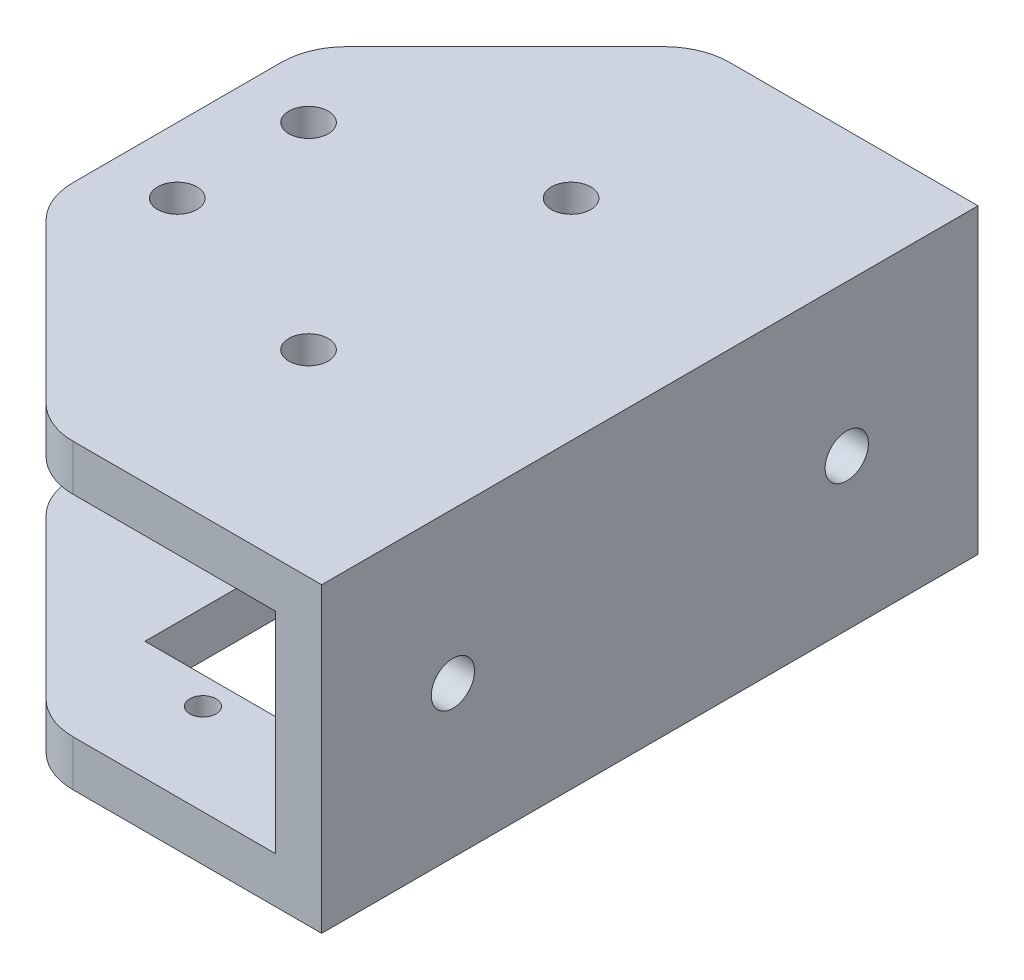
SolidWorks part; units mm, degrees
material "PMMA"
ref_plane "前视基准面" through (0, 0, 0) normal (0, 0, 1) x (1, 0, 0)
ref_plane "上视基准面" through (0, 0, 0) normal (0, 1, 0) x (1, 0, 0)
ref_plane "右视基准面" through (0, 0, 0) normal (1, 0, 0) x (0, 0, -1)
sketch "草图1" plane through (0, 0, 0) normal (0, 0, 1) x (1, 0, 0)
  line L0 (-45, 11.5) -> (0, 11.5)
  line L1 (0, 11.5) -> (0, -11.5)
  line L2 (0, -11.5) -> (-45, -11.5)
  line L3 (-45, 8) -> (-3.5, 8)
  line L4 (-3.5, 8) -> (-3.5, -8)
  line L5 (-3.5, -8) -> (-45, -8)
  line L6 (-45, 11.5) -> (-45, 8)
  line L7 (-45, -8) -> (-45, -11.5)
  dimension "D1" = 3.5
  dimension "D2" = 23
  dimension "D3" = 45
extrude "凸台-拉伸1" add sketch "草图1" along normal blind 50
sketch "草图2" plane through (0, -11.5, 0) normal (0, -1, 0) x (1, 0, 0)
  line L0 (0, 50) -> (0, 0) construction
  line L1 (-16, 25) -> (-40.6813, 25) construction
  line L2 (-16, 35) -> (-16, 50) construction
  line L3 (-45, 50) -> (0, 50) construction
  line L4 (-16, 15) -> (-16, 0) construction
  line L5 (-45, 0) -> (0, 0) construction
  circle A0 centre (-16, 35) radius 10 construction
  circle A1 centre (-16, 15) radius 10 construction
  circle A2 centre (-16, 35) radius 1.5
  circle A3 centre (-16, 15) radius 1.5
  circle A4 centre (-31, 30) radius 1.5
  circle A5 centre (-31, 20) radius 1.5
  dimension "D1" = 20
  dimension "D3" = 3
  dimension "D4" = 3
  dimension "D2" = 16
  dimension "D5" = 5
  dimension "D6" = 15
extrude "切除-拉伸1" cut sketch "草图2" against normal blind 70 from surface starting at face at (-24.25, 8, 25)
sketch "草图3" plane through (0, -11.5, 0) normal (0, -1, 0) x (1, 0, 0)
  line L0 (-21, 0) -> (-36, 15)
  line L1 (-45, 0) -> (0, 0) construction
  line L2 (-36, 15) -> (-36, 35)
  line L3 (-36, 35) -> (-21, 50)
  line L4 (-45, 50) -> (0, 50) construction
  line L6 (-40.6813, 25) -> (-23.9708, 25) construction
  line L7 (-21, 0) -> (0, 0)
  line L8 (0, 0) -> (0, 50)
  line L9 (0, 50) -> (-21, 50)
  dimension "D1" = 20
  dimension "D2" = 15
  dimension "D3" = 21
extrude "切除-拉伸2" cut sketch "草图3" against normal blind 70 flip side to cut
extrude "切除-拉伸4" cut sketch "草图2<3>" against normal blind 10 contours A4 | A5
sketch "草图2<3>" plane through (0, -11.5, 0) normal (0, -1, 0) x (1, 0, 0) same geometry as "草图2"
sketch "草图4" plane through (0, 11.5, 0) normal (0, 1, 0) x (1, 0, 0)
  line L0 (-16, -15.375) -> (-16, -43.045) construction
  circle A0 centre (-16, -35) radius 1.5 construction
  circle A1 centre (-16, -35) radius 1.5 construction
  dimension "D1" = 19.625
  dimension "D2" = 8.045
sketch "草图5" plane through (0, -11.5, 0) normal (0, -1, 0) x (1, 0, 0)
  line L0 (-16, 15.375) -> (-16, 43.045) construction
  line L1 (-16, 15.375) -> (-16, 43.045) construction
  circle A0 centre (-16, 43.045) radius 1
  circle A1 centre (-16, 15.375) radius 1
  dimension "D1" = 2
extrude "切除-拉伸5" cut sketch "草图5" against normal blind 10
fillet "圆角1" radius 5 8 edges at (-36, -9.75, 15) (-36, -9.75, 35) (-36, 9.75, 35) (-36, 9.75, 15) (-21, -9.75, 0) (-21, 9.75, 0) (-21, -9.75, 50) (-21, 9.75, 50)
sketch "草图6" plane through (0, -11.5, 0) normal (0, -1, 0) x (1, 0, 0)
  line L0 (-16, 15.375) -> (-16, 43.045) construction
  line L2 (-9.5, 17.46) -> (-22.5, 17.46)
  line L3 (-9.5, 17.46) -> (-9.5, 40.96)
  line L4 (-9.5, 40.96) -> (-22.5, 40.96)
  line L5 (-22.5, 17.46) -> (-22.5, 40.96)
  line L6 (-9.5, 17.46) -> (-22.5, 40.96) construction
  line L7 (-9.5, 40.96) -> (-22.5, 17.46) construction
  circle A0 centre (-16, 43.045) radius 1 construction
  circle A1 centre (-16, 43.045) radius 1 construction
  circle A2 centre (-16, 15.375) radius 1 construction
  circle A3 centre (-16, 15.375) radius 1 construction
  point P6 (-16, 29.21)
  dimension "D1" = 23.5
  dimension "D2" = 13
extrude "切除-拉伸6" cut sketch "草图6" against normal blind 10
sketch "草图7" plane through (0, 0, 0) normal (1, 0, 0) x (0, 0, -1)
  line L0 (0, 0) -> (-54.0378, 0) construction
  line L1 (-50, -11.5) -> (-50, 11.5) construction
  line L2 (0, -11.5) -> (0, 11.5) construction
  circle A0 centre (-10, 0) radius 1.65
  circle A1 centre (-40, 0) radius 1.65
  dimension "D1" = 3.3
  dimension "D2" = 10
  dimension "D3" = 10
extrude "切除-拉伸7" cut sketch "草图7" against normal blind 10
